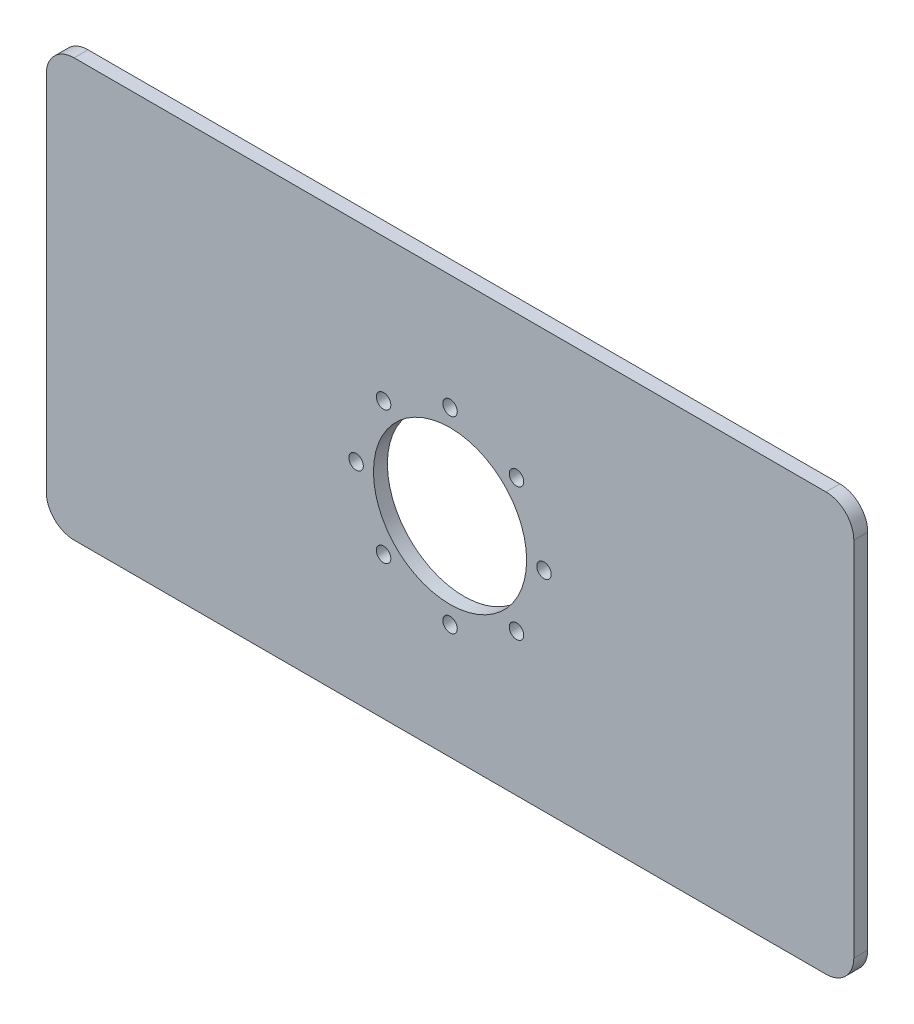
SolidWorks part; units mm, degrees
material "默认 (3)"
ref_plane "前视基准面" through (0, 0, 0) normal (0, 0, 1) x (1, 0, 0)
ref_plane "上视基准面" through (0, 0, 0) normal (0, 1, 0) x (1, 0, 0)
ref_plane "右视基准面" through (0, 0, 0) normal (1, 0, 0) x (0, 0, -1)
other "Configuration Table"
sketch "草图1" plane through (0, 0, 0) normal (0, 0, 1) x (1, 0, 0)
  line L1 (-145, 75) -> (145, 75)
  line L2 (-145, 75) -> (-145, -75)
  line L3 (-145, -75) -> (145, -75)
  line L4 (145, 75) -> (145, -75)
  line L5 (-145, 75) -> (145, -75) construction
  line L6 (-145, -75) -> (145, 75) construction
  point P0 (0, 0)
  dimension "D1" = 150
  dimension "D2" = 290
extrude "凸台-拉伸1" add sketch "草图1" along normal blind 5
sketch "草图5" plane through (0, 0, 0) normal (0, 0, -1) x (-1, 0, 0)
  circle A1 centre (0, 0) radius 27.5
  circle A2 centre (0, 0) radius 27.5
  circle A3 centre (23.8649, 23.8649) radius 2.6
  circle A4 centre (23.8649, 23.8649) radius 2.6
  circle A5 centre (0, 33.75) radius 2.6
  circle A6 centre (0, 33.75) radius 2.6
  circle A7 centre (-23.8649, 23.8649) radius 2.6
  circle A8 centre (-23.8649, 23.8649) radius 2.6
  circle A9 centre (-33.75, 0) radius 2.6
  circle A10 centre (-33.75, 0) radius 2.6
  circle A11 centre (-23.8649, -23.8649) radius 2.6
  circle A12 centre (-23.8649, -23.8649) radius 2.6
  circle A13 centre (0, -33.75) radius 2.6
  circle A14 centre (0, -33.75) radius 2.6
  circle A15 centre (23.8649, -23.8649) radius 2.6
  circle A16 centre (23.8649, -23.8649) radius 2.6
  circle A17 centre (33.75, 0) radius 2.6
  circle A18 centre (33.75, 0) radius 2.6
  dimension "D1" = 0
  dimension "D2" = 0
  dimension "D3" = 0
  dimension "D4" = 0
  dimension "D5" = 0
  dimension "D6" = 0
  dimension "D7" = 0
  dimension "D8" = 0
  dimension "D9" = 0
extrude "切除-拉伸2" cut sketch "草图5" against normal up to next
fillet "圆角1" radius 10 4 edges at (145, 75, 2.5) (145, -75, 2.5) (-145, -75, 2.5) (-145, 75, 2.5)
